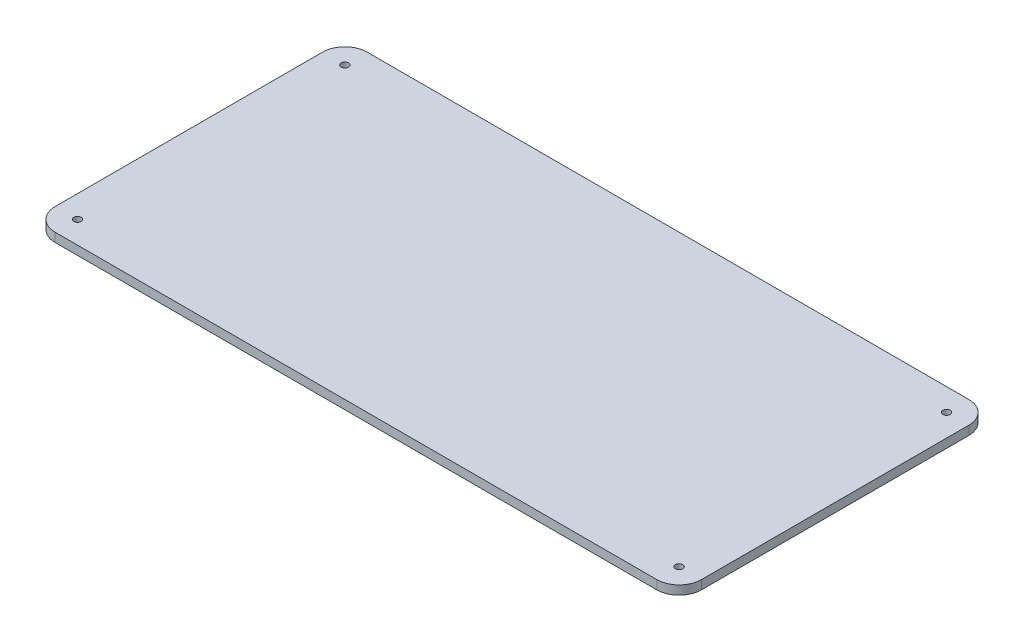
SolidWorks part; units mm, degrees
ref_plane "Front Plane" through (0, 0, 0) normal (0, 0, 1) x (1, 0, 0)
ref_plane "Top Plane" through (0, 0, 0) normal (0, 1, 0) x (1, 0, 0)
ref_plane "Right Plane" through (0, 0, 0) normal (1, 0, 0) x (0, 0, -1)
sketch "Sketch1" plane through (0, 0, 0) normal (0, 1, 0) x (1, 0, 0)
  line L0 (0, 0) -> (145, 0) construction
  line L1 (145, 0) -> (145, -60)
  line L2 (135, -70) -> (0, -70)
  line L3 (0, -70) -> (0, 0)
  line L4 (0, 0) -> (145, 0)
  arc A0 (135, -70) -> (145, -60) centre (135, -60) ccw
  circle A1 centre (135, -60) radius 1.65
  point P7 (145, -70)
  dimension "D4" = 10
  dimension "D5" = 3.3
  dimension "D1" = 145
  dimension "D2" = 70
  dimension "D3" = 145
extrude "Boss-Extrude1" add sketch "Sketch1" along normal blind 4 contours L2 A0 L1 L4 L3 A1 region at (72.2982, 0, 34.9094)
mirror "Mirror1" about plane through (0, 0, 0) normal (1, 0, 0) of "Boss-Extrude1"
mirror "Mirror2" about plane through (0, 0, 0) normal (0, 0, 1) of "Mirror1"
